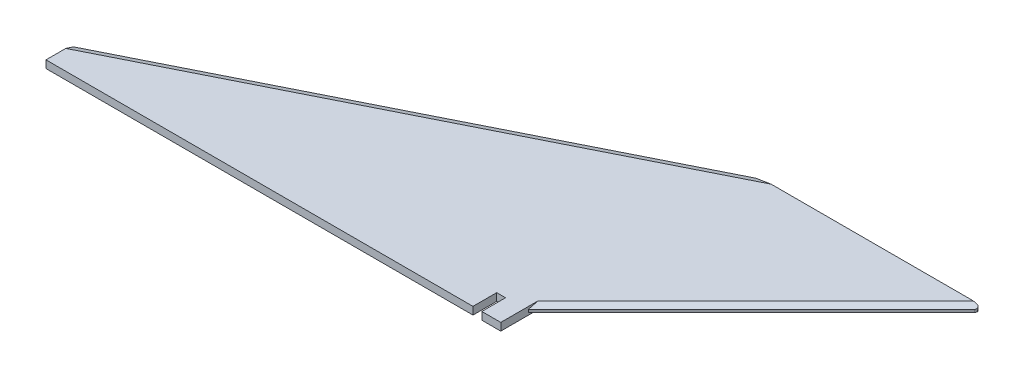
SolidWorks part; units mm, degrees
material "A-Glass Fiber"
ref_plane "Front Plane" through (0, 0, 0) normal (0, 0, 1) x (1, 0, 0)
ref_plane "Top Plane" through (0, 0, 0) normal (0, 1, 0) x (1, 0, 0)
ref_plane "Right Plane" through (0, 0, 0) normal (1, 0, 0) x (0, 0, -1)
sketch "Sketch1" plane through (0, 0, 0) normal (0, 1, 0) x (1, 0, 0)
  line L0 (0, 0) -> (0, 10.9)
  line L1 (0, 10.9) -> (180, 100.9)
  line L2 (180, 100.9) -> (270, 100.9)
  line L3 (270, 100.9) -> (180, 10.9)
  line L4 (180, 10.9) -> (180, 0)
  line L5 (180, 0) -> (172.5, 0)
  line L6 (172.5, 0) -> (172.5, 9.4)
  line L7 (172.5, 9.4) -> (169, 9.4)
  line L8 (169, 9.4) -> (169, 0)
  line L9 (169, 0) -> (0, 0)
  line L10 (-989.0676, -29) -> (49010.9324, -29) construction
  line L11 (-1000, 0) -> (49000, 0) construction
  line L12 (-999.3384, -58) -> (49000.6616, -58) construction
  line L13 (0, 0) -> (0, -58) construction
  point P15 (0, -29)
  point P19 (179.1478, 26.8947)
  dimension "D1" = 90
  dimension "D2" = 180
  dimension "D3" = 1.5
  dimension "D4" = 180
  dimension "D5" = 90
  dimension "D6" = 79.8
  dimension "D7" = 58
  dimension "D8" = 3.5
  dimension "D9" = 7.5
extrude "Boss-Extrude1" add sketch "Sketch1" along normal blind 3
chamfer "Chamfer1" distance 1 angle 70 2 edges at (225, 3, -55.9) (90, 3, -55.9) first distance on face at (225, 1.5, -55.9) first distance on face at (90, 1.5, -55.9)
chamfer "Chamfer2" distance 1 angle 70 2 edges at (90, 0, -55.9) (225, 0, -55.9) first distance on face at (90, 1, -55.9) first distance on face at (225, 1, -55.9)
fillet "Fillet1" radius 1 1 edges at (270, 1.5, -100.9)
